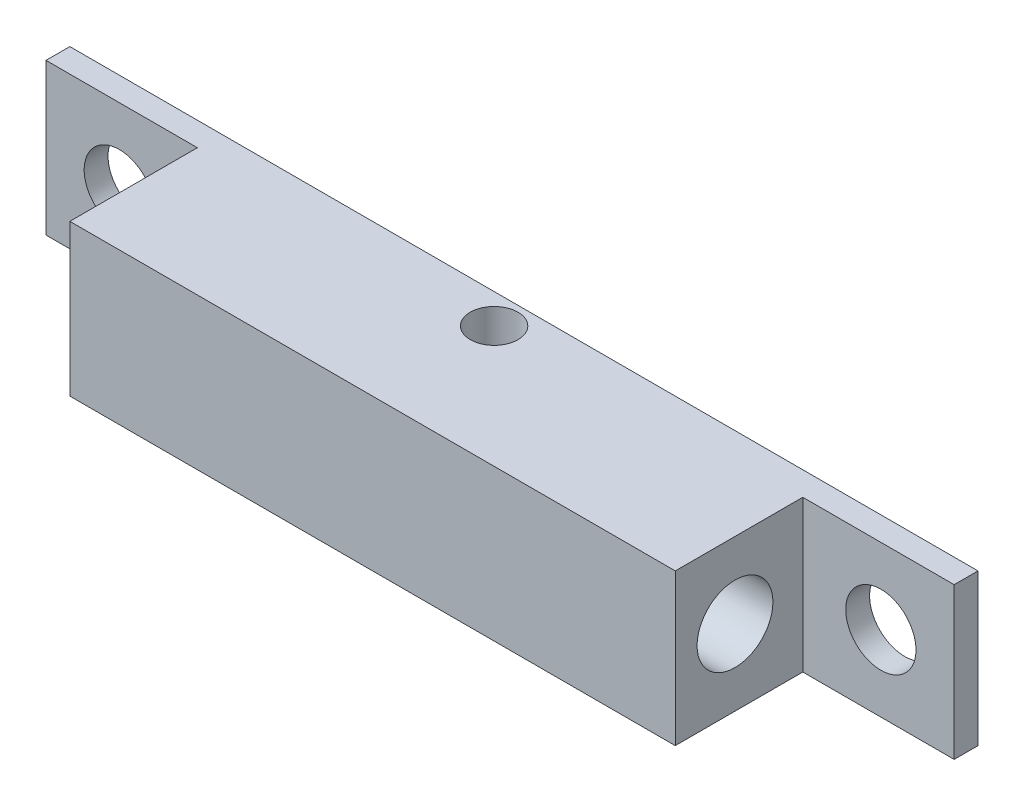
SolidWorks part; units mm, degrees
other "Markup1"
sketch "Sketch4" plane through (-6.35, -10, 15) normal (-0.3542, -0.9351, 0.0128) x (0.9346, -0.3545, -0.0309)
other "Markup2"
sketch "Sketch5" plane through (-6.35, 0, 6.35) normal (-0.9896, 0.1407, 0.0289) x (0.0558, 0.1909, 0.98)
material "6061 Alloy"
ref_plane "Front Plane" through (0, 0, 0) normal (0, 0, 1) x (1, 0, 0)
ref_plane "Top Plane" through (0, 0, 0) normal (0, 1, 0) x (1, 0, 0)
ref_plane "Right Plane" through (0, 0, 0) normal (1, 0, 0) x (0, 0, -1)
sketch "Sketch1" plane through (0, 0, 0) normal (0, 0, 1) x (1, 0, 0)
  line L1 (0, 0) -> (25.4, 0)
  line L2 (0, 0) -> (0, -6.35)
  line L3 (0, -6.35) -> (25.4, -6.35)
  line L4 (25.4, 0) -> (25.4, -6.35)
  line L5 (0, 0) -> (-6.35, 0)
  line L6 (0, 0) -> (0, -6.35)
  line L7 (0, -6.35) -> (-6.35, -6.35)
  line L8 (-6.35, 0) -> (-6.35, -6.35)
  line L9 (25.4, 0) -> (31.75, 0)
  line L10 (25.4, 0) -> (25.4, -6.35)
  line L11 (25.4, -6.35) -> (31.75, -6.35)
  line L12 (31.75, 0) -> (31.75, -6.35)
  circle A0 centre (-3.275, -3.175) radius 1.4732
  circle A1 centre (28.675, -3.175) radius 1.4732
  circle A2 centre (-3.275, -3.175) radius 2.3241 construction
  circle A3 centre (28.675, -3.175) radius 2.3241 construction
  point P19 (-6.35, -3.175)
  dimension "D1" = 2.9464
  dimension "D10" = 4.6482
  dimension "D11" = 4.6482
  dimension "D2" = 25.4
  dimension "D3" = 6.35
  dimension "D4" = 3.275
  dimension "D5" = 3.275
  dimension "D7" = 3.175
  dimension "D8" = 6.35
  dimension "D9" = 3.175
extrude "Boss-Extrude1" add sketch "Sketch1" along normal blind 1 contours L5 L8 L7 L2 A0 | L12 L9 L4 L11 A1 region at (-0.0898, -3.175, 0) region at (28.575, -0.0898, 0)
extrude "Boss-Extrude2" add sketch "Sketch1<3>" along normal blind 6.35 contours L4 L1 L2 L3 region at (12.7, -3.175, 0)
sketch "Sketch1<3>" plane through (0, 0, 0) normal (0, 0, 1) x (1, 0, 0) same geometry as "Sketch1"
sketch "Sketch2" plane through (0, 0, 0) normal (-1, 0, 0) x (0, 0, 1)
  line L1 (3.8448, 0) -> (3.8448, -6.35) construction
  line L2 (6.35, 0) -> (1, 0) construction
  line L3 (6.35, -6.35) -> (1, -6.35) construction
  line L4 (1, 0) -> (1, -6.35) construction
  circle A0 centre (3.8448, -3.175) radius 1.591
  dimension "D1" = 3.182
  dimension "D2" = 2.8448
  dimension "D3" = 0
  dimension "D4" = 3.175
extrude "Cut-Extrude1" cut sketch "Sketch2" against normal up to surface (25.4 mm away)
sketch "Sketch3" plane through (0, 0, 0) normal (0, 1, 0) x (1, 0, 0)
  line L0 (0, -6.35) -> (0, -1) construction
  line L2 (-6.35, 0) -> (31.75, 0) construction
  circle A0 centre (12.7, -1.25) radius 1
  dimension "D1" = 2
  dimension "D2" = 12.7
  dimension "D3" = 1.25
extrude "Cut-Extrude2" cut sketch "Sketch3" against normal up to surface (6.35 mm away) contours A0 up to face at (12.7, -6.35, 2.0875)
equation "\"D4@Sketch1\"=(\"D3@Sketch1\")/2+0.1"
equation "\"D5@Sketch1\"=\"D4@Sketch1\""
equation "\"D7@Sketch1\"=\"D8@Sketch1\"/2"
equation "\"D9@Sketch1\"=\"D8@Sketch1\"/2"
